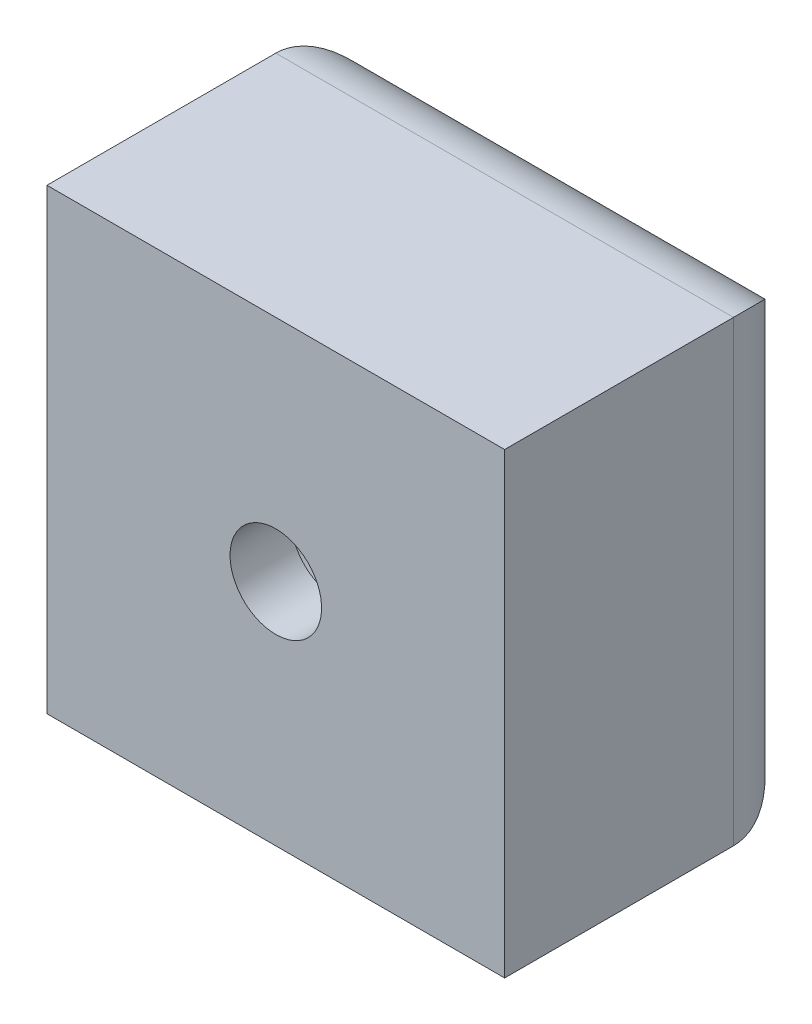
SolidWorks part; units mm, degrees
ref_plane "Front Plane" through (0, 0, 0) normal (0, 0, 1) x (1, 0, 0)
ref_plane "Top Plane" through (0, 0, 0) normal (0, 1, 0) x (1, 0, 0)
ref_plane "Right Plane" through (0, 0, 0) normal (1, 0, 0) x (0, 0, -1)
sketch "Sketch1" plane through (0, 0, 0) normal (0, 0, 1) x (1, 0, 0)
  line L1 (0, 0) -> (15, 0)
  line L2 (0, 0) -> (0, 15)
  line L3 (0, 15) -> (15, 15)
  line L4 (15, 0) -> (15, 15)
  dimension "D1" = 15
  dimension "D2" = 15
extrude "Boss-Extrude1" add sketch "Sketch1" along normal blind 10
fillet "Fillet2" radius 2.5 4 edges at (7.5, 0, 0) (15, 7.5, 0) (7.5, 15, 0) (0, 7.5, 0)
hole_wizard "M3x0.5 Tapped Hole1" positions "Sketch3" profile "Sketch4" tap size "M3x0.5" standard "ANSI Metric" end condition through all
sketch "Sketch3" plane through (0, 0, 0) normal (0, 0, -1) x (-1, 0, 0)
  line L0 (-7.5, 2.5) -> (-7.5, 12.5) construction
  line L1 (-12.5, 2.5) -> (-2.5, 2.5) construction
  line L2 (-2.5, 12.5) -> (-12.5, 12.5) construction
  line L5 (-12.5, 7.5) -> (-2.5, 7.5) construction
  line L6 (-12.5, 12.5) -> (-12.5, 2.5) construction
  line L7 (-2.5, 2.5) -> (-2.5, 12.5) construction
  point P20 (-7.5, 7.5)
sketch "Sketch4" plane through (7.5, 7.5, 0) normal (1, 0, 0) x (0, 1, 0)
  line L0 (0, 0) -> (0, 10)
  line L1 (0, 10) -> (1.5, 10)
  line L2 (1.5, 10) -> (1.5, 0)
  line L5 (1.5, 0) -> (0, 0)
  line L11 (0, -6.35) -> (0, 107.95) construction
  dimension "Thread Major Dia." = 3
  dimension "Thru Tap Drill Depth" = 10
sketch "Sketch5" plane through (0, 0, 0) normal (0, 0, -1) x (-1, 0, 0)
  line L0 (-12.5, 7.5) -> (-2.5, 7.5) construction
  line L1 (-12.5, 12.5) -> (-12.5, 2.5) construction
  line L2 (-2.5, 2.5) -> (-2.5, 12.5) construction
  line L3 (-7.5, 2.5) -> (-7.5, 12.5) construction
  line L4 (-12.5, 2.5) -> (-2.5, 2.5) construction
  line L5 (-2.5, 12.5) -> (-12.5, 12.5) construction
  circle A0 centre (-7.5, 7.5) radius 3
  dimension "D1" = 6
extrude "Cut-Extrude1" cut sketch "Sketch5" against normal blind 8
